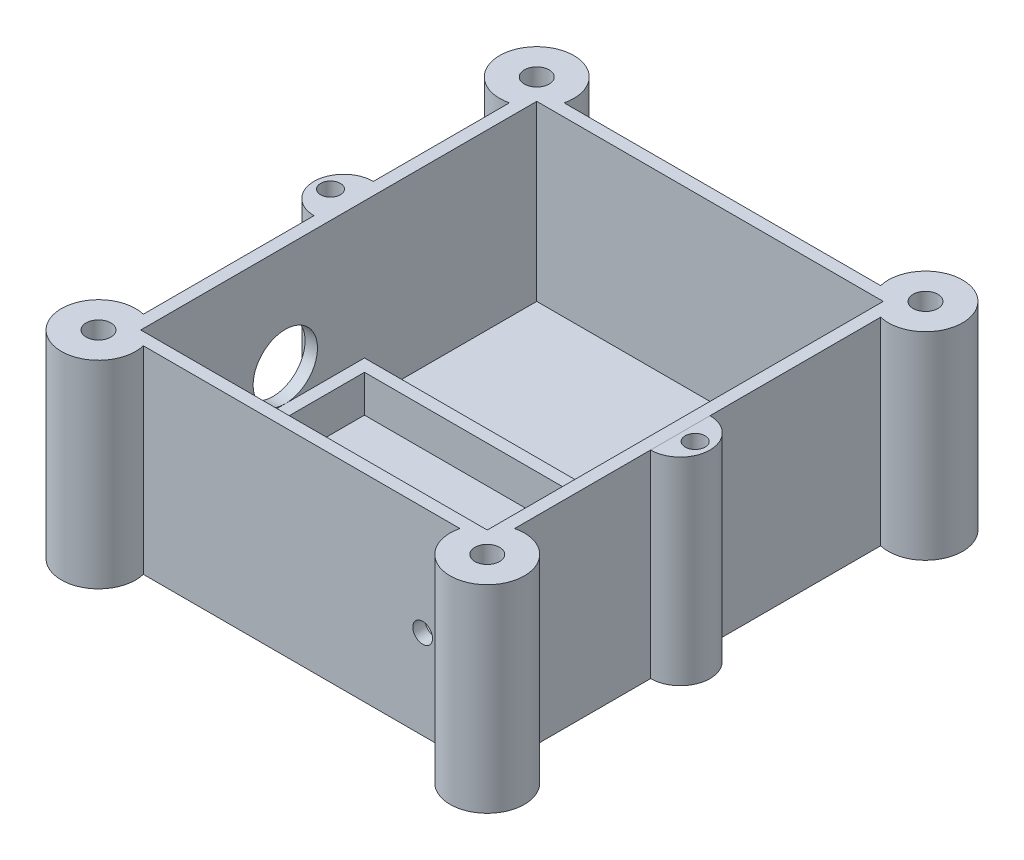
SolidWorks part; units mm, degrees
ref_plane "Front Plane" through (0, 0, 0) normal (0, 0, 1) x (1, 0, 0)
ref_plane "Top Plane" through (0, 0, 0) normal (0, 1, 0) x (1, 0, 0)
ref_plane "Right Plane" through (0, 0, 0) normal (1, 0, 0) x (0, 0, -1)
sketch "Sketch1" plane through (0, 0, 0) normal (0, 1, 0) x (1, 0, 0)
  line L0 (-97.4951, 2.2451) -> (-95.25, 0) construction
  line L1 (-7.0116, 0) -> (-88.2384, 0)
  line L2 (0, -7.0116) -> (0, -100.9384)
  line L3 (-7.0116, -107.95) -> (-88.2384, -107.95)
  line L4 (-95.25, -7.0116) -> (-95.25, -100.9384)
  line L5 (-3.175, -3.175) -> (-92.075, -3.175)
  line L6 (-3.175, -3.175) -> (-3.175, -104.775)
  line L7 (-3.175, -104.775) -> (-92.075, -104.775)
  line L8 (-92.075, -3.175) -> (-92.075, -104.775)
  line L9 (2.2451, 2.2451) -> (0, 0) construction
  line L10 (2.2451, -110.1951) -> (0, -107.95) construction
  line L11 (-97.4951, -110.1951) -> (-95.25, -107.95) construction
  circle A0 centre (-97.4951, 2.2451) radius 3.175
  arc A1 (-88.2384, 0) -> (-95.25, -7.0116) centre (-97.4951, 2.2451) ccw
  circle A2 centre (2.2451, 2.2451) radius 3.175
  arc A3 (0, -7.0116) -> (-7.0116, 0) centre (2.2451, 2.2451) ccw
  circle A4 centre (2.2451, -110.1951) radius 3.175
  arc A5 (-7.0116, -107.95) -> (0, -100.9384) centre (2.2451, -110.1951) ccw
  circle A6 centre (-97.4951, -110.1951) radius 3.175
  arc A7 (-95.25, -100.9384) -> (-88.2384, -107.95) centre (-97.4951, -110.1951) ccw
  point P23 (0, 0)
  dimension "D11" = 6.35
  dimension "D12" = 6.35
  dimension "D13" = 6.35
  dimension "D14" = 6.35
  dimension "D15" = 6.35
  dimension "D16" = 6.35
  dimension "D17" = 6.35
  dimension "D18" = 6.35
  dimension "D1" = 107.95
  dimension "D2" = 95.25
  dimension "D3" = 88.9
  dimension "D4" = 101.6
  dimension "D5" = 3.175
  dimension "D6" = 3.175
  dimension "D7" = 135
  dimension "D8" = 135
  dimension "D9" = 135
  dimension "D10" = 135
extrude "Boss-Extrude1" add sketch "Sketch1" along normal blind 6.35 contours L4 A7 L3 A5 L2 A3 L1 A1 | A2 | A4 | A6 | A0
extrude "Boss-Extrude2" add sketch "Sketch1<3>" along normal blind 50.8
sketch "Sketch1<3>" plane through (0, 0, 0) normal (0, 1, 0) x (1, 0, 0) same geometry as "Sketch1"
sketch "Sketch3" plane through (0, 0, 107.95) normal (0, 0, 1) x (1, 0, 0)
  line L0 (-7.0116, 0) -> (-88.2384, 0) construction
  line L1 (0, 50.8) -> (0, 0) construction
  circle A0 centre (-16.5661, 22.86) radius 2.54
  dimension "D1" = 5.08
  dimension "D2" = 22.86
  dimension "D3" = 16.5661
extrude "Cut-Extrude1" cut sketch "Sketch3" against normal blind 12.7
sketch "Sketch5" plane through (0, 0, 0) normal (1, 0, 0) x (0, 0, -1)
  line L0 (-100.9384, 50.8) -> (-7.0116, 50.8) construction
  line L1 (-66.04, 50.8) -> (-58.42, 50.8)
  line L2 (-66.04, 50.8) -> (-66.04, 0)
  line L3 (-66.04, 0) -> (-58.42, 0)
  line L4 (-58.42, 50.8) -> (-58.42, 0)
  line L5 (-7.0116, 0) -> (-100.9384, 0) construction
  dimension "D1" = 7.62
revolve "Revolve1" add sketch "Sketch5" angle 180 about L4 reverse direction yes
sketch "Sketch6" plane through (-95.25, 0, 0) normal (-1, 0, 0) x (0, 0, 1)
  line L0 (7.0116, 50.8) -> (100.9384, 50.8) construction
  line L1 (49.53, 50.8) -> (57.15, 50.8)
  line L2 (49.53, 50.8) -> (49.53, 0)
  line L3 (49.53, 0) -> (57.15, 0)
  line L4 (57.15, 50.8) -> (57.15, 0)
  line L5 (7.0116, 0) -> (100.9384, 0) construction
  dimension "D1" = 7.62
revolve "Revolve2" add sketch "Sketch6" angle 180 about L2
sketch "Sketch7" plane through (0, 50.8, 0) normal (0, 1, 0) x (1, 0, 0)
  circle A0 centre (-99.039, -49.1303) radius 2.54
  arc A9 (-95.25, -41.91) -> (-95.25, -57.15) centre (-95.25, -49.53) ccw construction
  dimension "D1" = 5.08
  dimension "D2" = 3.81
  dimension "D3" = 3.789
extrude "Cut-Extrude2" cut sketch "Sketch7" against normal through all
sketch "Sketch9" plane through (0, 50.8, 0) normal (0, 1, 0) x (1, 0, 0)
  line L0 (0, -100.9384) -> (0, -7.0116) construction
  circle A0 centre (3.81, -58.42) radius 2.54
  arc A1 (0, -66.04) -> (0, -50.8) centre (0, -58.42) ccw construction
  dimension "D1" = 5.08
  dimension "D2" = 3.81
  dimension "D3" = 3.81
extrude "Cut-Extrude3" cut sketch "Sketch9" against normal through all
sketch "Sketch10" plane through (0, 6.35, 0) normal (0, 1, 0) x (1, 0, 0)
  line L0 (-92.075, -104.775) -> (-92.075, -3.175) construction
  line L1 (-92.075, -104.775) -> (-3.175, -104.775)
  line L2 (-92.075, -104.775) -> (-92.075, -47.371)
  line L3 (-92.075, -47.371) -> (-3.175, -47.371)
  line L4 (-3.175, -104.775) -> (-3.175, -47.371)
  line L6 (-88.9, -101.6) -> (-7.366, -101.6)
  line L7 (-88.9, -101.6) -> (-88.9, -50.546)
  line L8 (-88.9, -50.546) -> (-7.366, -50.546)
  line L9 (-7.366, -101.6) -> (-7.366, -50.546)
  dimension "D1" = 3.175
  dimension "D2" = 3.175
  dimension "D3" = 3.175
  dimension "D4" = 4.191
  dimension "D5" = 51.054
  dimension "D6" = 81.534
extrude "Boss-Extrude3" add sketch "Sketch10" along normal blind 9.525
sketch "Sketch11" plane through (0, 6.35, 0) normal (0, 1, 0) x (1, 0, 0)
  line L0 (-73.533, -74.4855) -> (-73.533, -50.546) construction
  line L1 (-22.733, -74.4855) -> (-73.533, -74.4855)
  line L2 (-22.733, -74.4855) -> (-22.733, -77.6605)
  line L3 (-22.733, -77.6605) -> (-73.533, -77.6605)
  line L4 (-73.533, -74.4855) -> (-73.533, -77.6605)
  line L5 (-7.366, -50.546) -> (-88.9, -50.546) construction
  line L6 (-73.533, -77.6605) -> (-73.533, -101.6) construction
  line L7 (-88.9, -101.6) -> (-7.366, -101.6) construction
  line L8 (-73.533, -75.356) -> (-88.9, -75.356) construction
  line L9 (-88.9, -50.546) -> (-88.9, -101.6) construction
  line L10 (-22.733, -75.356) -> (-7.366, -75.356) construction
  line L11 (-7.366, -101.6) -> (-7.366, -50.546) construction
  dimension "D1" = 3.175
  dimension "D2" = 50.8
extrude "Boss-Extrude4" add sketch "Sketch11" along normal blind 5.08
sketch "Sketch12" plane through (-95.25, 0, 0) normal (-1, 0, 0) x (0, 0, 1)
  line L1 (57.15, 0) -> (100.9384, 0) construction
  line L2 (57.15, 0) -> (57.15, 50.8) construction
  circle A0 centre (67.691, 24.13) radius 8.255
  dimension "D1" = 16.51
  dimension "D2" = 10.541
  dimension "D3" = 24.13
extrude "Cut-Extrude4" cut sketch "Sketch12" against normal blind 7.62
fillet "Fillet1" radius 3.175 4 edges at (-97.4951, 0, 113.3701) (2.2451, 0, 113.3701) (-97.4951, 0, 0.9299) (2.2451, 0, 0.9299)
